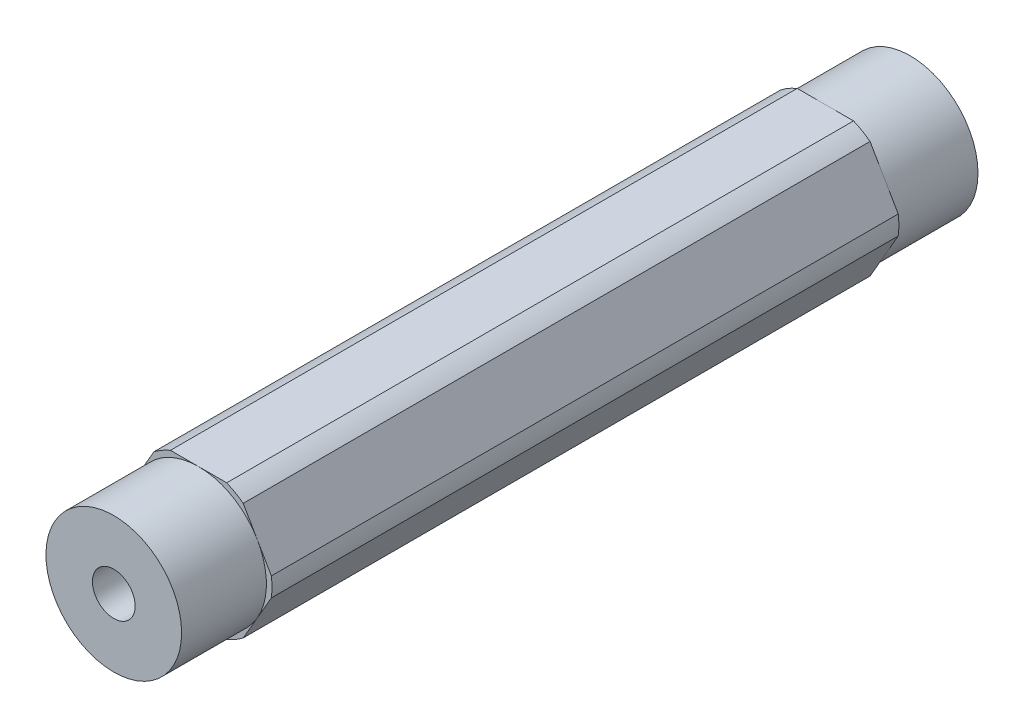
SolidWorks part; units mm, degrees
material "6061-T6 (SS)"
ref_plane "Front Plane" through (0, 0, 0) normal (0, 0, 1) x (1, 0, 0)
ref_plane "Top Plane" through (0, 0, 0) normal (0, 1, 0) x (1, 0, 0)
ref_plane "Right Plane" through (0, 0, 0) normal (1, 0, 0) x (0, 0, -1)
sketch "Sketch1" plane through (0, 0, 0) normal (0, 0, 1) x (1, 0, 0)
  line L1 (3.6662, 6.35) -> (-3.6662, 6.35)
  line L2 (-3.6662, 6.35) -> (-7.3323, 0)
  line L3 (-7.3323, 0) -> (-3.6662, -6.35)
  line L4 (-3.6662, -6.35) -> (3.6662, -6.35)
  line L5 (3.6662, -6.35) -> (7.3323, 0)
  line L6 (7.3323, 0) -> (3.6662, 6.35)
  circle A0 centre (0, 0) radius 6.35 construction
  circle A1 centre (0, 0) radius 2
  circle A2 centre (0, 0) radius 6.875
  point P1 (0, 6.35)
  dimension "D2" = 13.75
  dimension "D3" = 4
  dimension "D1" = 12.7
extrude "Boss-Extrude1" add sketch "Sketch1" along normal mid plane 58.6867 contours L6 A2 L1 L2 L3 L4 L5 A1 region at (3.3439, 5.7918, 0)
sketch "Sketch4" plane through (0, 0, 29.3434) normal (0, 0, 1) x (1, 0, 0)
  circle A0 centre (0, 0) radius 6.35
  circle A1 centre (0, 0) radius 2 construction
  circle A2 centre (0, 0) radius 2
  dimension "D1" = 12.7
extrude "Boss-Extrude2" add sketch "Sketch4" along normal blind 7.9375
mirror "Mirror1" about plane through (0, 0, 0) normal (0, 0, 1) of "Boss-Extrude2"
equation "\"D2@Sketch1\"=13.75mm"
equation "\"D3@Sketch1\"=4mm"
